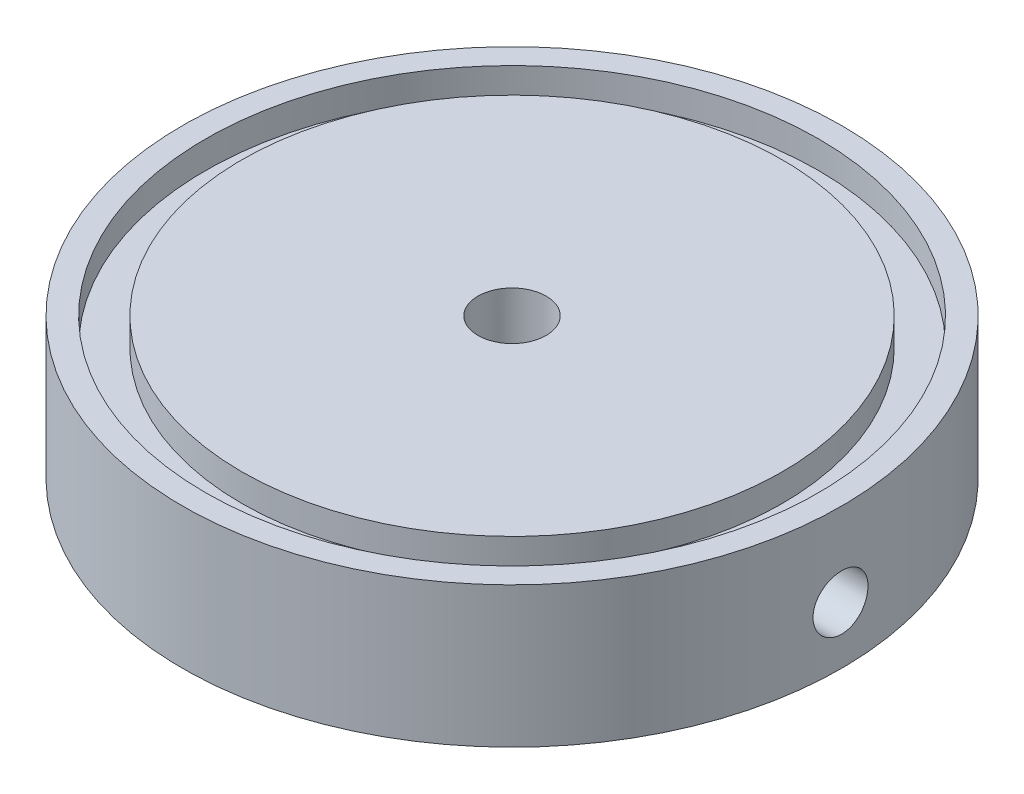
SolidWorks part; units mm, degrees
ref_plane "Front Plane" through (0, 0, 0) normal (0, 0, 1) x (1, 0, 0)
ref_plane "Top Plane" through (0, 0, 0) normal (0, 1, 0) x (1, 0, 0)
ref_plane "Right Plane" through (0, 0, 0) normal (1, 0, 0) x (0, 0, -1)
sketch "Sketch1" plane through (0, 0, 0) normal (0, 0, 1) x (1, 0, 0)
  line L0 (0, 101.6046) -> (0, 116.1639) construction
  line L1 (3.9434, 7.4346) -> (38.1, 7.4346)
  line L2 (3.9434, 7.4346) -> (3.9434, 0)
  line L3 (10.9855, -8.8265) -> (21.1455, -8.8265)
  line L4 (3.9434, 0) -> (9.4615, -4.064)
  line L5 (38.1, 7.4346) -> (38.1, -8.8214)
  line L7 (21.1455, -8.8265) -> (21.1455, -7.8105)
  line L8 (21.1455, -7.8105) -> (22.6695, -7.8105)
  line L9 (22.6695, -7.8105) -> (22.6695, -8.8214)
  line L10 (22.6695, -8.8214) -> (38.1, -8.8214)
  line L12 (10.9855, -6.3919) -> (10.9855, -8.8265)
  arc A0 (10.9855, -6.3919) -> (9.4615, -4.064) centre (8.4455, -6.3919) ccw
  dimension "D9" = 2.54
  dimension "D1" = 3.9434
  dimension "D5" = 1.524
  dimension "D6" = 1.016
  dimension "D2" = 38.1
  dimension "D4" = 7.4346
  dimension "D7" = 10.9855
  dimension "D3" = 1.524
  dimension "D10" = 10.16
  dimension "D13" = 16.256
  dimension "D8" = 8.8265
revolve "Revolve1" add sketch "Sketch1" angle 360 about L0
sketch "Sketch2" plane through (0, 0, 0) normal (1, 0, 0) x (0, 0, -1)
  line L0 (-38.1, -8.8214) -> (38.1, -8.8214) construction
  circle A0 centre (0, -2.2174) radius 1.7272
  dimension "D1" = 6.604
extrude "Cut-Extrude1" cut sketch "Sketch2" along normal through all
sketch "Sketch3" plane through (0, 7.4346, 0) normal (0, 1, 0) x (1, 0, 0)
  circle A0 centre (0, 0) radius 31.242
  circle A1 centre (0, 0) radius 35.433
extrude "Cut-Extrude2" cut sketch "Sketch3" against normal blind 3.175
ref_plane "Plane1" through (0, -8.8214, 0) normal (0, -1, 0) x (-1, 0, 0)
sketch "Sketch4" plane through (0, -8.8214, 0) normal (0, -1, 0) x (-1, 0, 0)
  line L0 (0, 0) -> (-13.97, 24.1967) construction
  circle A0 centre (-13.97, 24.1967) radius 1.0325
  circle A1 centre (0, 0) radius 27.94 construction
  dimension "D2" = 55.88
extrude "Cut-Extrude3" cut sketch "Sketch4" against normal blind 3.175
ref_axis "Axis1" through (0, 7.4346, 0) along (0, -1, 0)
pattern_circular "CirPattern1" count 9 over 360 about axis through (0, 7.4346, 0) along (0, -1, 0) of "Cut-Extrude3"
ref_plane "Plane2" through (38.1, 0, 0) normal (1, 0, 0) x (0, 0, -1)
ref_axis "Axis2" through (38.1, -2.2174, 0) along (-1, 0, 0)
sketch "Sketch5" plane through (38.1, 0, 0) normal (1, 0, 0) x (0, 0, -1)
  circle A0 centre (0, -2.2174) radius 3.175
  dimension "D1" = 6.35
extrude "Cut-Extrude4" cut sketch "Sketch5" against normal blind 9.525
fillet "Fillet1" radius 1.27 1 edges at (0, 0, -3.9433)
equation "\"ManifoldChamberThickness\"= 0.3475"
equation "\"AnnulusLength\"= 0.2927"
equation "\"D8@Sketch1\"=\"ManifoldChamberThickness\""
equation "\"D4@Sketch1\"=\"AnnulusLength\""
equation "\"AnnulusDiameter\"= 0.3105"
equation "\"D1@Sketch1\"=\"AnnulusDiameter\"/2"
